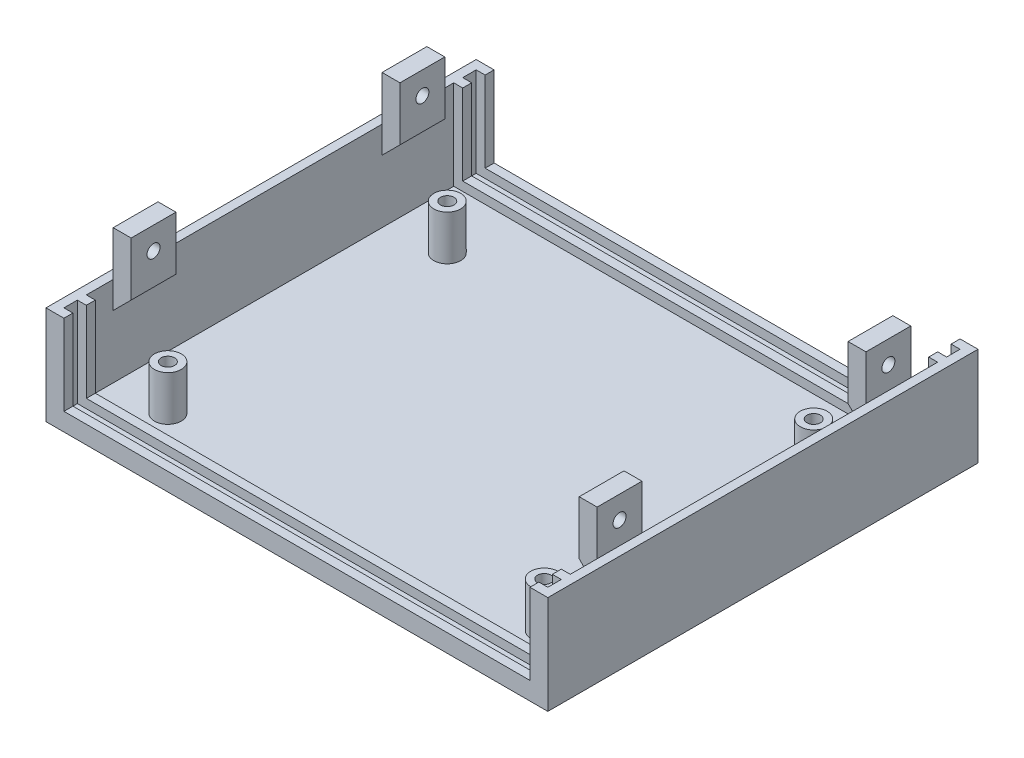
SolidWorks part; units mm, degrees
ref_plane "Plano frontal" through (0, 0, 0) normal (0, 0, 1) x (1, 0, 0)
ref_plane "Plano superior" through (0, 0, 0) normal (0, 1, 0) x (1, 0, 0)
ref_plane "Plano direito" through (0, 0, 0) normal (1, 0, 0) x (0, 0, -1)
sketch "Esboço1" plane through (0, 0, 0) normal (0, 1, 0) x (1, 0, 0)
  line L1 (0, 0) -> (112, 0)
  line L2 (0, 0) -> (0, 96)
  line L3 (0, 96) -> (112, 96)
  line L4 (112, 0) -> (112, 96)
  dimension "D1" = 96
  dimension "D2" = 112
extrude "Ressalto-extrusão1" add sketch "Esboço1" along normal blind 2
sketch "Esboço2" plane through (0, 2, 0) normal (0, 1, 0) x (1, 0, 0)
  line L0 (0, 0) -> (112, 0) construction
  line L1 (0, 96) -> (2, 96)
  line L2 (0, 96) -> (0, 0)
  line L3 (0, 0) -> (2, 0)
  line L4 (2, 96) -> (2, 0)
  line L6 (112, 96) -> (110, 96)
  line L7 (112, 96) -> (112, 0)
  line L8 (112, 0) -> (110, 0)
  line L9 (110, 96) -> (110, 0)
  dimension "D1" = 2
  dimension "D2" = 2
extrude "Ressalto-extrusão2" add sketch "Esboço2" along normal blind 20
sketch "Esboço3" plane through (0, 2, 0) normal (0, 1, 0) x (1, 0, 0)
  line L0 (110, 96) -> (110, 0) construction
  line L1 (2, 96) -> (110, 96)
  line L2 (2, 96) -> (2, 94)
  line L3 (2, 94) -> (110, 94)
  line L4 (110, 96) -> (110, 94)
  line L5 (2, 0) -> (2, 96) construction
  line L6 (110, 0) -> (2, 0)
  line L7 (110, 0) -> (110, 2)
  line L8 (110, 2) -> (2, 2)
  line L9 (2, 0) -> (2, 2)
  line L10 (2, 0) -> (2, 96) construction
  line L11 (110, 91) -> (2, 91)
  line L12 (110, 91) -> (110, 89)
  line L13 (110, 89) -> (2, 89)
  line L14 (2, 91) -> (2, 89)
  line L16 (110, 7) -> (2, 7)
  line L17 (110, 7) -> (110, 5)
  line L18 (110, 5) -> (2, 5)
  line L19 (2, 7) -> (2, 5)
  dimension "D1" = 2
  dimension "D2" = 2
  dimension "D3" = 3
  dimension "D4" = 2
  dimension "D5" = 3
  dimension "D6" = 2
extrude "Ressalto-extrusão3" add sketch "Esboço3" along normal blind 20
sketch "Esboço5" plane through (0, 0, 0) normal (0, 0, 1) x (1, 0, 0)
  line L0 (0, 22) -> (112, 22) construction
  line L1 (4, 22) -> (108, 22)
  line L2 (4, 22) -> (4, 4)
  line L3 (4, 4) -> (108, 4)
  line L4 (108, 22) -> (108, 4)
  line L5 (0, 0) -> (112, 0) construction
  line L6 (0, 22) -> (0, 0) construction
  line L7 (112, 22) -> (112, 0) construction
  dimension "D1" = 4
  dimension "D2" = 4
  dimension "D3" = 4
extrude "Corte-extrusão1" cut sketch "Esboço5" against normal through all
sketch "Esboço6" plane through (0, 2, 0) normal (0, 1, 0) x (1, 0, 0)
  line L0 (110, 13.2) -> (2, 13.2) construction
  line L1 (110, 89) -> (110, 7) construction
  line L2 (2, 7) -> (2, 89) construction
  line L3 (2, 5) -> (110, 5) construction
  line L4 (112, 0) -> (112, 96) construction
  circle A0 centre (98, 13.2) radius 3
  circle A1 centre (14, 13.2) radius 3
  circle A2 centre (97.143, 74.194) radius 3
  circle A3 centre (14.1518, 75.4) radius 3
  dimension "D2" = 84
  dimension "D8" = 6
  dimension "D9" = 6
  dimension "D10" = 6
  dimension "D11" = 6
  dimension "D1" = 8.2
  dimension "D3" = 83
  dimension "D4" = 61
  dimension "D5" = 104.4
  dimension "D6" = 62.2
  dimension "D7" = 14
extrude "Ressalto-extrusão4" add sketch "Esboço6" along normal blind 10
sketch "Esboço7" plane through (0, 12, 0) normal (0, 1, 0) x (1, 0, 0)
  circle A0 centre (14.1518, 75.4) radius 1.5
  circle A1 centre (97.143, 74.194) radius 1.5
  circle A2 centre (98, 13.2) radius 1.5
  circle A3 centre (14, 13.2) radius 1.5
  dimension "D1" = 3
  dimension "D2" = 3
  dimension "D3" = 3
  dimension "D4" = 3
extrude "Corte-extrusão2" cut sketch "Esboço7" against normal blind 10
sketch "Esboço8" plane through (110, 0, 0) normal (-1, 0, 0) x (0, 0, 1)
  line L0 (-78, 2) -> (-78, 33.5826) construction
  line L1 (-89, 2) -> (-7, 2) construction
  line L2 (-18, 2) -> (-18, 33.5826) construction
  line L3 (-96, 4) -> (-96, 22) construction
  line L5 (-89, 22) -> (-7, 22) construction
  line L6 (-83, 16) -> (-73, 16)
  line L7 (-83, 16) -> (-83, 32)
  line L8 (-83, 32) -> (-73, 32)
  line L9 (-73, 16) -> (-73, 32)
  line L10 (-23, 16) -> (-13, 16)
  line L11 (-23, 16) -> (-23, 32)
  line L12 (-23, 32) -> (-13, 32)
  line L13 (-13, 16) -> (-13, 32)
  dimension "D1" = 60
  dimension "D2" = 18
  dimension "D3" = 16
  dimension "D4" = 6
  dimension "D5" = 16
  dimension "D6" = 6
  dimension "D7" = 10
  dimension "D8" = 10
  dimension "D9" = 5
  dimension "D10" = 5
extrude "Ressalto-extrusão5" add sketch "Esboço8" along normal blind 4
sketch "Esboço9" plane through (2, 0, 0) normal (1, 0, 0) x (0, 0, -1)
  line L0 (7, 22) -> (89, 22) construction
  line L1 (13, 32) -> (23, 32)
  line L2 (13, 32) -> (13, 16)
  line L3 (13, 16) -> (23, 16)
  line L4 (23, 32) -> (23, 16)
  line L5 (73, 32) -> (83, 32)
  line L6 (73, 32) -> (73, 16)
  line L7 (73, 16) -> (83, 16)
  line L8 (83, 32) -> (83, 16)
  line L9 (0, 22) -> (0, 4) construction
  point P10 (18, 32)
  dimension "D1" = 16
  dimension "D2" = 16
  dimension "D3" = 10
  dimension "D4" = 10
  dimension "D5" = 6
  dimension "D6" = 6
  dimension "D7" = 60
  dimension "D8" = 18
extrude "Ressalto-extrusão6" add sketch "Esboço9" along normal blind 4
sketch "Esboço10" plane through (110, 0, 0) normal (1, 0, 0) x (0, 0, -1)
  line L0 (23, 22) -> (13, 22) construction
  line L1 (83, 22) -> (73, 22) construction
  line L2 (13, 22) -> (13, 32) construction
  circle A0 centre (18, 27) radius 1.45
  circle A1 centre (78, 27) radius 1.45
  dimension "D1" = 2.9
  dimension "D2" = 2.9
  dimension "D3" = 5
  dimension "D4" = 5
  dimension "D5" = 60
  dimension "D6" = 5
extrude "Corte-extrusão3" cut sketch "Esboço10" against normal through all
chamfer "Chanfro2" distance 4 angle 45 4 edges at (106, 16, -18) (106, 16, -78) (6, 16, -78) (6, 16, -18)
